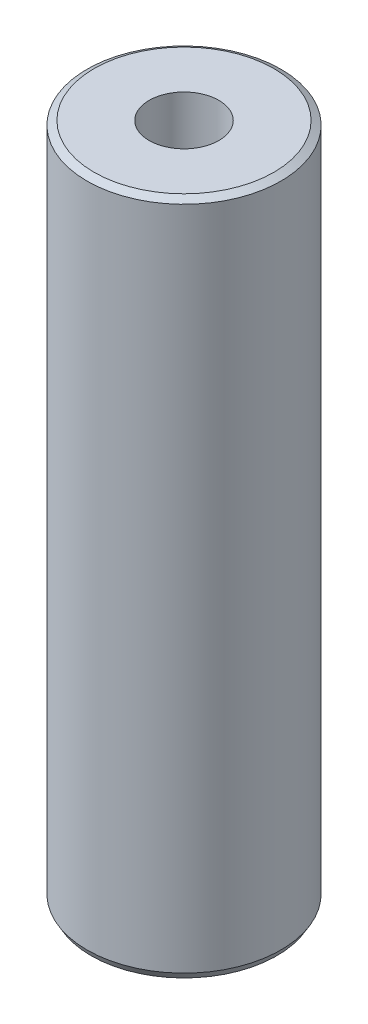
SolidWorks part; units mm, degrees
ref_plane "Front Plane" through (0, 0, 0) normal (0, 0, 1) x (1, 0, 0)
ref_plane "Top Plane" through (0, 0, 0) normal (0, 1, 0) x (1, 0, 0)
ref_plane "Right Plane" through (0, 0, 0) normal (1, 0, 0) x (0, 0, -1)
sketch "Sketch1" plane through (0, 0, 0) normal (0, 1, 0) x (1, 0, 0)
  circle A0 centre (0, 0) radius 17.5
  dimension "SHAFT_OD" = 35
extrude "Boss-Extrude1" add sketch "Sketch1" along normal blind 122.192
sketch "Sketch2" plane through (0, 0, 0) normal (0, 1, 0) x (1, 0, 0)
  circle A0 centre (0, 0) radius 6.2905
  dimension "BORE_D" = 12.5811
extrude "Cut-Extrude1" cut sketch "Sketch2" along normal through all
chamfer "Chamfer1" distance 0.7373 angle 60 2 edges at (0, 122.192, 17.5) (0, 0, 17.5) first distance on face at (0, 122.192, 17.5) first distance on face at (0, 0, 6.2905)
